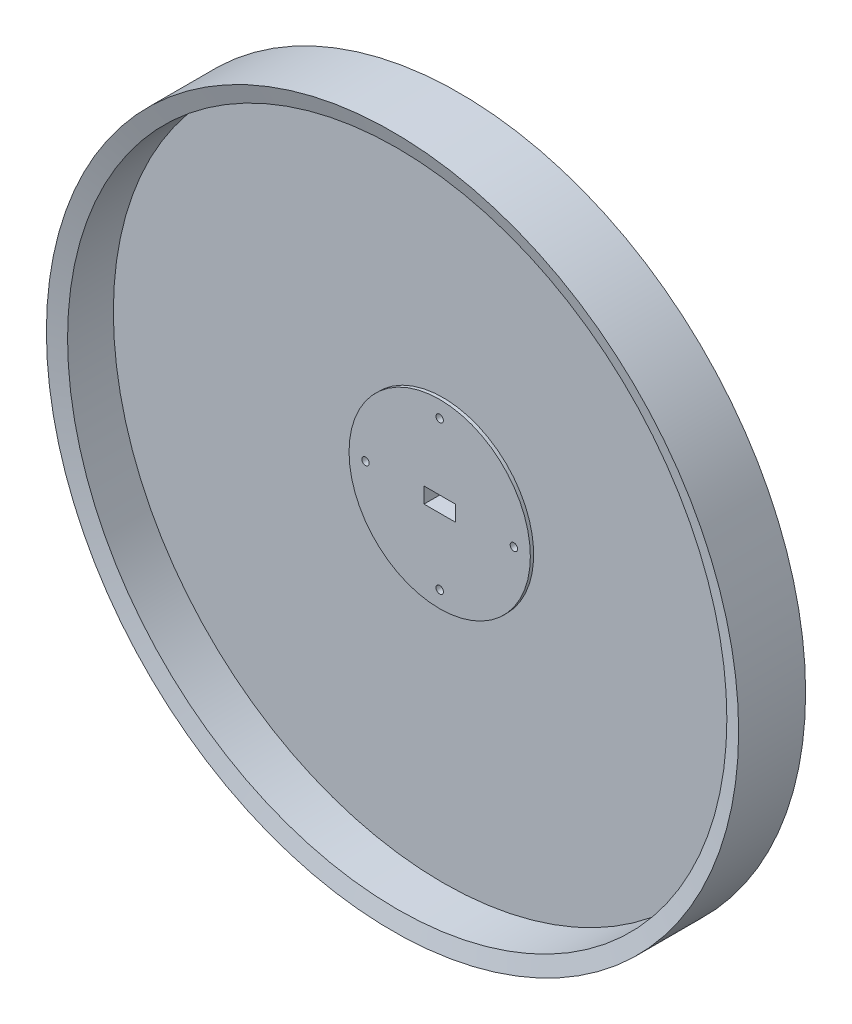
SolidWorks part; units mm, degrees
ref_plane "Спереди" through (0, 0, 0) normal (0, 0, 1) x (1, 0, 0)
ref_plane "Сверху" through (0, 0, 0) normal (0, 1, 0) x (1, 0, 0)
ref_plane "Справа" through (0, 0, 0) normal (1, 0, 0) x (0, 0, -1)
sketch "Эскиз1" plane through (0, 0, 0) normal (0, 1, 0) x (1, 0, 0)
  line L0 (0, 0) -> (200, 0)
  line L6 (210, 10) -> (0, 10)
  line L7 (0, 10) -> (0, 0)
  line L8 (200, 0) -> (200, -27.7778)
  line L9 (200, -27.7778) -> (210, -30.625)
  line L10 (210, -30.625) -> (210, 10)
  parabola Q0 (800, -444.4444) -> (0, 0) focus (0, -360) apex (0, 0) construction
  dimension "D1" = 360
  dimension "D2" = 800
  dimension "D3" = 200
  dimension "D4" = 10
  dimension "D5" = 210
revolve "Повернуть1" add sketch "Эскиз1" angle 360 about L7
sketch "Эскиз2" plane through (0, 0, 0) normal (0, 0, 1) x (1, 0, 0)
  line L1 (-9.5, -4.75) -> (9.5, -4.75)
  line L2 (-9.5, -4.75) -> (-9.5, 4.75)
  line L3 (-9.5, 4.75) -> (9.5, 4.75)
  line L4 (9.5, -4.75) -> (9.5, 4.75)
  line L5 (-9.5, -4.75) -> (9.5, 4.75) construction
  line L6 (-9.5, 4.75) -> (9.5, -4.75) construction
  point P0 (0, 0)
  dimension "D1" = 19
  dimension "D2" = 9.5
extrude "Вырез-Вытянуть1" cut sketch "Эскиз2" against normal through all and the other way through all
sketch "Эскиз3" plane through (0, 0, 0) normal (0, 0, 1) x (1, 0, 0)
  circle A0 centre (0, 0) radius 55
extrude "Бобышка-Вытянуть1" add sketch "Эскиз3" along normal blind 2
sketch "Эскиз4" plane through (0, 0, 2) normal (0, 0, 1) x (1, 0, 0)
  line L1 (-9.5, -4.75) -> (9.5, -4.75)
  line L2 (-9.5, -4.75) -> (-9.5, 4.75)
  line L3 (-9.5, 4.75) -> (9.5, 4.75)
  line L4 (9.5, -4.75) -> (9.5, 4.75)
  line L5 (-9.5, -4.75) -> (9.5, 4.75) construction
  line L6 (-9.5, 4.75) -> (9.5, -4.75) construction
  point P0 (0, 0)
  dimension "D1" = 19
  dimension "D2" = 9.5
extrude "Вырез-Вытянуть2" cut sketch "Эскиз4" against normal blind 2
sketch "Эскиз6" plane through (0, 0, 2) normal (0, 0, 1) x (1, 0, 0)
  line L0 (0, 0) -> (0, 45) construction
hole_wizard "Отверстие с зазором M41" positions "Трехмерный эскиз1" profile "Эскиз8" hole size "M4" standard "ISO" end condition through all
sketch3d "Трехмерный эскиз1"
  point P0 (0, 45, 2)
sketch "Эскиз8" plane through (0, 45, 2) normal (1, 0, 0) x (0, -1, 0)
  line L0 (0, 0) -> (0, 12)
  line L1 (0, 12) -> (2.25, 12)
  line L2 (2.25, 12) -> (2.25, 0)
  line L5 (2.25, 0) -> (0, 0)
  line L11 (0, -6.35) -> (0, 107.95) construction
  dimension "Диаметр сквозного отверстия" = 4.5
  dimension "Глубина сквозного отверстия" = 12
ref_axis "Ось1" through (0, 0, 0) along (0, 0, 1)
pattern_circular "Круговой массив1" count 4 every 90 about axis through (0, 0, 0) along (0, 0, 1) of "Отверстие с зазором M41"
sketch "Эскиз9" plane through (0, 0, -10) normal (0, 0, -1) x (-1, 0, 0)
  line L1 (-14.5, -15) -> (14.5, -15) construction
  line L2 (-14.5, -15) -> (-14.5, 15) construction
  line L3 (-14.5, 15) -> (14.5, 15) construction
  line L4 (14.5, -15) -> (14.5, 15) construction
  line L5 (-14.5, -15) -> (14.5, 15) construction
  line L6 (-14.5, 15) -> (14.5, -15) construction
  point P0 (0, 0)
  dimension "D1" = 29
  dimension "D2" = 30
hole_wizard "Отверстие с зазором M42" positions "Трехмерный эскиз2" profile "Эскиз10" hole size "M4" standard "ISO"
sketch3d "Трехмерный эскиз2"
  point P0 (-14.5, 15, -10)
  point P4 (14.5, 15, -10)
  point P7 (14.5, -15, -10)
  point P10 (-14.5, -15, -10)
sketch "Эскиз10" plane through (-14.5, 15, -10) normal (1, 0, 0) x (0, 1, 0)
  line L0 (0, 0) -> (0, 11.3519)
  line L1 (0, 11.3519) -> (2.25, 10)
  line L2 (2.25, 10) -> (2.25, 0.025)
  line L3 (2.25, 0.025) -> (2.275, 0)
  line L5 (2.275, 0) -> (0, 0)
  line L6 (-2.25, 0.025) -> (-2.275, 0) construction
  line L10 (0, 11.3519) -> (-2.25, 10) construction
  line L11 (0, -6.35) -> (0, 107.95) construction
  dimension "Диаметр отверстия" = 4.5
  dimension "Глубина отверстия" = 10
  dimension "Диаметр передней зенковки" = 4.55
  dimension "Угол передней зенковки" = 90
  dimension "Угол заточки сверла" = 118
